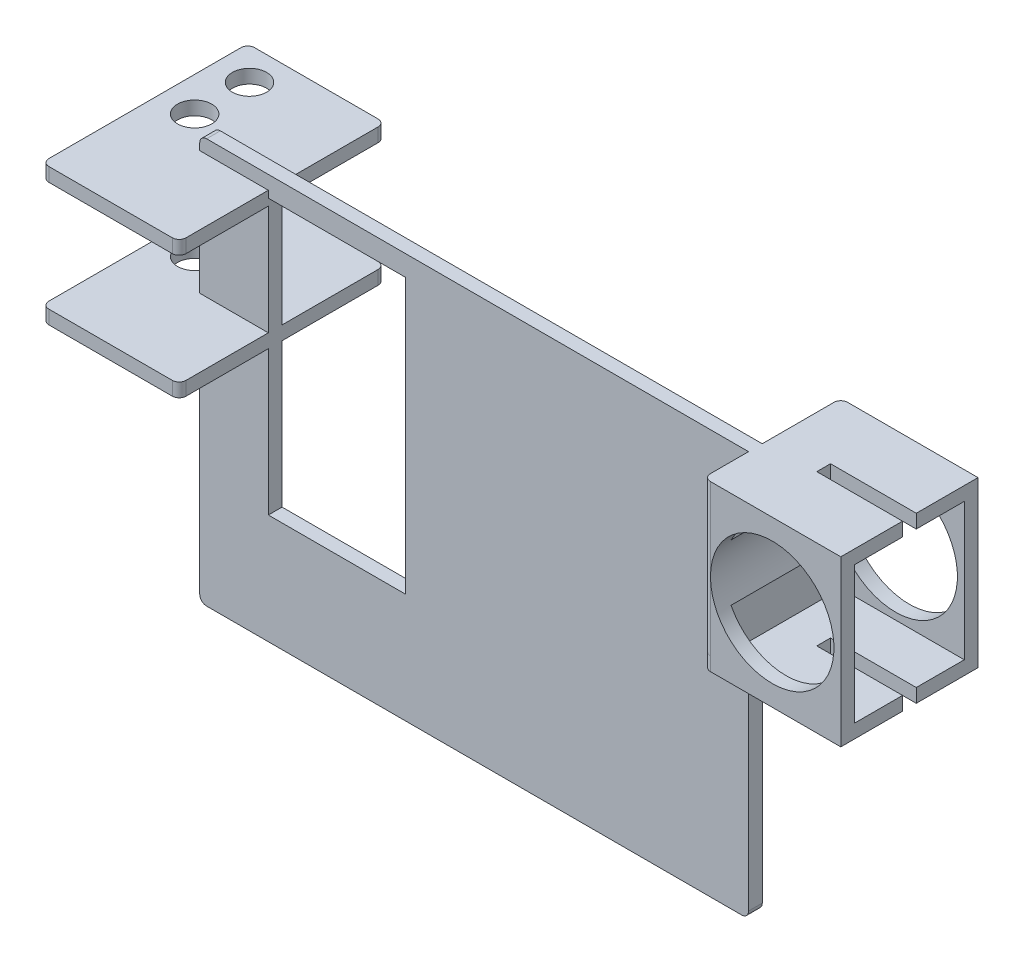
SolidWorks part; units mm, degrees
ref_plane "Front Plane" through (0, 0, 0) normal (0, 0, 1) x (1, 0, 0)
ref_plane "Top Plane" through (0, 0, 0) normal (0, 1, 0) x (1, 0, 0)
ref_plane "Right Plane" through (0, 0, 0) normal (1, 0, 0) x (0, 0, -1)
sketch "Sketch1" plane through (0, 0, 0) normal (0, 1, 0) x (1, 0, 0)
  line L0 (-2.2917, 11.0417) -> (-22.2917, 11.0417)
  line L1 (-22.2917, 11.0417) -> (-22.2917, -8.9583)
  line L2 (-22.2917, -8.9583) -> (-2.2917, -8.9583)
  line L3 (-20.2917, 9.0417) -> (-2.2917, 9.0417)
  line L4 (-20.2917, 9.0417) -> (-20.2917, -6.9583)
  line L5 (-20.2917, -6.9583) -> (-2.2917, -6.9583)
  line L6 (-2.2917, -6.9583) -> (-2.2917, -8.9583)
  line L7 (-2.2917, 9.0417) -> (-2.2917, 11.0417)
  dimension "D1" = 20
  dimension "D2" = 20
  dimension "D3" = 20
  dimension "D4" = 2
  dimension "D5" = 2
  dimension "D6" = 2
extrude "Boss-Extrude1" add sketch "Sketch1" along normal blind 20
fillet "Fillet1" radius 1 2 edges at (-22.2917, 10, -11.0417) (-22.2917, 10, 8.9583)
sketch "Sketch2" plane through (0, 0, 8.9583) normal (0, 0, 1) x (1, 0, 0)
  line L0 (-21.2917, 0) -> (-2.2917, 0) construction
  line L1 (-2.2917, 20) -> (-2.2917, 0) construction
  circle A0 centre (-12.2917, 10) radius 9
  dimension "D3" = 18
  dimension "D1" = 10
  dimension "D2" = 10
extrude "Cut-Extrude1" cut sketch "Sketch2" against normal blind 20
sketch "Sketch3" plane through (0, 20, 0) normal (0, 1, 0) x (1, 0, 0)
  line L0 (-21.2917, 11.0417) -> (-2.2917, 11.0417)
  line L1 (-2.2917, 11.0417) -> (-2.2917, -8.9583)
  line L2 (-2.2917, -8.9583) -> (-22.2917, -8.9583)
  line L3 (-22.2917, -8.9583) -> (-22.2917, 11.0417)
  line L4 (-22.2917, 11.0417) -> (-21.2917, 11.0417)
  line L9 (-2.2917, 2.3778) -> (-2.2917, 0.3778)
  line M10 (-2.2917, 11.0417) -> (-21.2917, 11.0417)
  arc M11 (-21.2917, 11.0417) -> (-22.2917, 10.0417) centre (-21.2917, 10.0417) ccw
  line M12 (-22.2917, 10.0417) -> (-22.2917, -7.9583)
  arc M13 (-22.2917, -7.9583) -> (-21.2917, -8.9583) centre (-21.2917, -7.9583) ccw
  line M14 (-21.2917, -8.9583) -> (-2.2917, -8.9583)
  line M15 (-2.2917, -8.9583) -> (-2.2917, -6.9583)
  line M16 (-2.2917, -6.9583) -> (-20.2917, -6.9583)
  line M17 (-20.2917, -6.9583) -> (-20.2917, 9.0417)
  line M18 (-20.2917, 9.0417) -> (-2.2917, 9.0417)
  line M19 (-2.2917, 9.0417) -> (-2.2917, 11.0417)
  dimension "D1" = 20
extrude "Boss-Extrude2" add sketch "Sketch3" along normal blind 2 contours L1 M18 M17 M16 | M19 M10 M11 M12 M13 M14 M15 M16 M17 M18 region at (-11.7917, 20, -10.7588) region at (-11.2917, 20, -1.0417)
sketch "Sketch4" plane through (0, 0, 0) normal (0, -1, 0) x (1, 0, 0)
  line L0 (-2.2917, 8.9583) -> (-2.2917, -11.0417)
  line L1 (-2.2917, -11.0417) -> (-22.2917, -11.0417)
  line L2 (-22.2917, -11.0417) -> (-22.2917, 8.9583)
  line L3 (-22.2917, 8.9583) -> (-2.2917, 8.9583)
  dimension "D1" = 20
  dimension "D2" = 20
extrude "Boss-Extrude3" add sketch "Sketch4" along normal blind 2
fillet "Fillet2" radius 1 2 edges at (-22.2917, -1, -11.0417) (-22.2917, -1, 8.9583)
sketch "Sketch5" plane through (0, 22, 0) normal (0, 1, 0) x (1, 0, 0)
  line L0 (-2.2917, 11.0417) -> (-2.2917, -8.9583) construction
  line L1 (-14.7917, 2.0417) -> (-2.2917, 2.0417)
  line L2 (-14.7917, 2.0417) -> (-14.7917, 0.0417)
  line L3 (-14.7917, 0.0417) -> (-2.2917, 0.0417)
  line L4 (-2.2917, 2.0417) -> (-2.2917, 0.0417)
  line L5 (-21.2917, -8.9583) -> (-2.2917, -8.9583) construction
  dimension "D1" = 12.5
  dimension "D2" = 2
  dimension "D3" = 9
extrude "Cut-Extrude2" cut sketch "Sketch5" against normal blind 24
sketch "Sketch6" plane through (-22.2917, 0, 0) normal (-1, 0, 0) x (0, 0, 1)
  line L0 (2.4083, -37) -> (0.4083, -37)
  line L5 (0.4083, -37) -> (0.4083, -2)
  line L6 (-10.0417, 22) -> (7.9583, 22) construction
  line L7 (2.4083, 22) -> (0.4083, 22)
  line L8 (2.4083, 22) -> (2.4083, -2)
  line L10 (0.4083, 22) -> (0.4083, -2)
  line L11 (7.9583, -2) -> (-10.0417, -2) construction
  line L13 (2.4083, -2) -> (2.4083, -37)
  line L14 (8.9583, 22) -> (8.9583, 10) construction
  point P6 (1.4083, -37)
  dimension "D1" = 6.55
  dimension "D2" = 2
  dimension "D3" = 35
extrude "Boss-Extrude4" add sketch "Sketch6" along normal blind 80
fillet "Fillet3" radius 1 3 edges at (-22.2917, -37, 1.4083) (-102.2917, -37, 1.4083) (-102.2917, 22, 1.4083)
sketch "Sketch8" plane through (0, 0, 0.4083) normal (0, 0, -1) x (-1, 0, 0)
  line L0 (82.2917, 22) -> (82.2917, -40.0805) construction
  line L1 (72.2917, 19) -> (92.2917, 19)
  line L2 (72.2917, 19) -> (72.2917, -21)
  line L3 (72.2917, -21) -> (92.2917, -21)
  line L4 (92.2917, 19) -> (92.2917, -21)
  line L5 (101.2917, 22) -> (22.2917, 22) construction
  line L6 (12.2917, 10) -> (131.172, 10) construction
  circle A0 centre (12.2917, 10) radius 9 construction
  circle A1 centre (12.2917, 10) radius 7.1139
  dimension "D4" = 70
  dimension "D1" = 20
  dimension "D2" = 40
  dimension "D3" = 10
  dimension "D5" = 9
extrude "Cut-Extrude3" cut sketch "Sketch8" against normal blind 2
sketch "Sketch9" plane through (0, 0, 0.4083) normal (0, 0, -1) x (-1, 0, 0)
  line L0 (92.471, 20) -> (102.2917, 20)
  line L1 (102.2917, 21) -> (102.2917, -36) construction
  line L3 (102.2917, 18) -> (92.2917, 18)
  line L4 (92.2917, -21) -> (92.2917, 19) construction
  line L5 (92.471, 20) -> (92.2917, 20)
  line L6 (92.2917, 20) -> (92.2917, 18)
  line L7 (92.2917, 2) -> (112.2917, 2)
  line L8 (112.2917, 2) -> (112.2917, 0)
  line L9 (112.2917, 0) -> (92.2917, 0)
  line L10 (92.2917, 0) -> (92.2917, 2)
  line L11 (102.2917, 20) -> (112.2917, 20)
  line L12 (112.2917, 20) -> (112.2917, 18)
  line L13 (112.2917, 18) -> (102.2917, 18)
  line L14 (101.2917, 22) -> (22.2917, 22) construction
  point P11 (97.2917, 18)
  dimension "D1" = 2
  dimension "D2" = 2
  dimension "D3" = 16
  dimension "D4" = 20
  dimension "D5" = 20
  dimension "D6" = 2
extrude "Boss-Extrude5" add sketch "Sketch9" along normal mid plane 30
fillet "Fillet4" radius 1 8 edges at (-112.2917, 19, -14.5917) (-112.2917, 1, 15.4083) (-112.2917, 19, 15.4083) (-112.2917, 1, -14.5917) (-92.2917, 1, 15.4083) (-92.2917, 19, 15.4083) (-92.2917, 19, -14.5917) (-92.2917, 1, -14.5917)
sketch "Sketch10" plane through (0, 0, 0) normal (0, -1, 0) x (1, 0, 0)
  line L1 (-92.2917, 0.4083) -> (-102.2917, 0.4083) construction
  line L4 (-102.2917, 0.4083) -> (-102.2917, -14.5917) construction
  line L5 (-93.2917, -14.5917) -> (-111.2917, -14.5917) construction
  line L6 (-107.2917, -17.4424) -> (-107.2917, 10.1065) construction
  circle A0 centre (-107.2917, -1.8487) radius 2.5
  circle A1 centre (-107.2917, -9.8487) radius 2.5
  point P24 (-107.2917, -16.5416)
  dimension "D4" = 5
  dimension "D5" = 5
  dimension "D3" = 5
  dimension "D6" = 8
  dimension "D9" = 5
extrude "Cut-Extrude4" cut sketch "Sketch10" against normal blind 20
